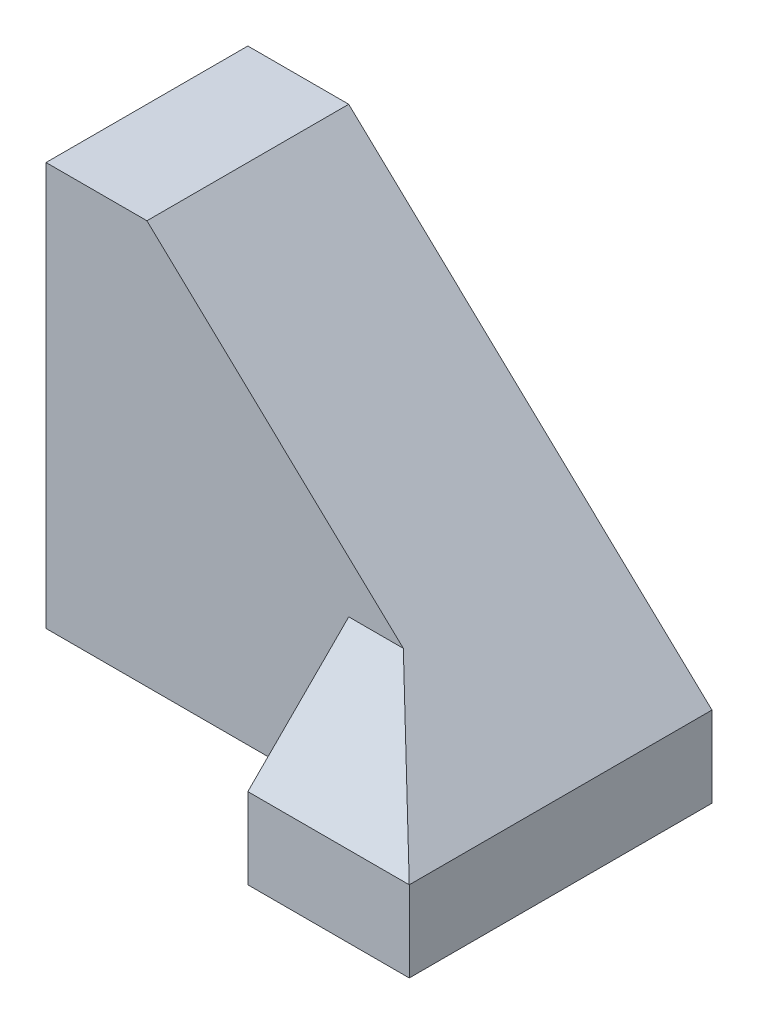
SolidWorks part; units mm, degrees
ref_plane "正面" through (0, 0, 0) normal (0, 0, 1) x (1, 0, 0)
ref_plane "平面" through (0, 0, 0) normal (0, 1, 0) x (1, 0, 0)
ref_plane "右側面" through (0, 0, 0) normal (1, 0, 0) x (0, 0, -1)
sketch "ｽｹｯﾁ1" plane through (0, 0, 0) normal (0, 0, 1) x (1, 0, 0)
  line L0 (0, 0) -> (0, 20)
  line L1 (0, 20) -> (5, 20)
  line L2 (5, 20) -> (23, 3)
  line L3 (23, 3) -> (23, 0)
  line L4 (23, 0) -> (0, 0)
  dimension "D1" = 20
  dimension "D2" = 5
  dimension "D3" = 3
  dimension "D4" = 23
extrude "ﾎﾞｽ - 押し出し1" add sketch "ｽｹｯﾁ1" along normal blind 10
sketch "ｽｹｯﾁ2" plane through (0, 0, 0) normal (-1, 0, 0) x (0, 0, 1)
  line L0 (10, 20) -> (10, 0) construction
  line L1 (10, 0) -> (0, 0) construction
  line L2 (10, 20) -> (0, 20) construction
  circle A0 centre (5, 15) radius 1.85
  circle A1 centre (5, 5) radius 1.85
  dimension "D1" = 3.7
  dimension "D2" = 3.7
  dimension "D3" = 5
  dimension "D4" = 5
  dimension "D5" = 5
  dimension "D6" = 5
extrude "ｶｯﾄ - 押し出し1" cut sketch "ｽｹｯﾁ2" against normal blind 6
sketch "ｽｹｯﾁ3" plane through (0, 0, 10) normal (0, 0, 1) x (1, 0, 0)
  line L0 (0, 0) -> (23, 0) construction
  line L1 (15, 0) -> (23, 0)
  line L2 (15, 0) -> (15, 3)
  line L3 (15, 3) -> (23, 3)
  line L4 (23, 0) -> (23, 3)
  dimension "D1" = 3
  dimension "D2" = 8
extrude "ﾎﾞｽ - 押し出し2" add sketch "ｽｹｯﾁ3" along normal blind 5
chamfer "面取り2" distance 5 angle 45 1 edges at (19, 3, 10)
sketch "ｽｹｯﾁ4" plane through (0, 0, 0) normal (0, -1, 0) x (-1, 0, 0)
  line L1 (-15, -15) -> (-23, -15)
  line L2 (-15, -15) -> (-15, 0)
  line L3 (-15, 0) -> (-23, 0)
  line L4 (-23, -15) -> (-23, 0)
extrude "ﾎﾞｽ - 押し出し3" add sketch "ｽｹｯﾁ4" along normal blind 1
